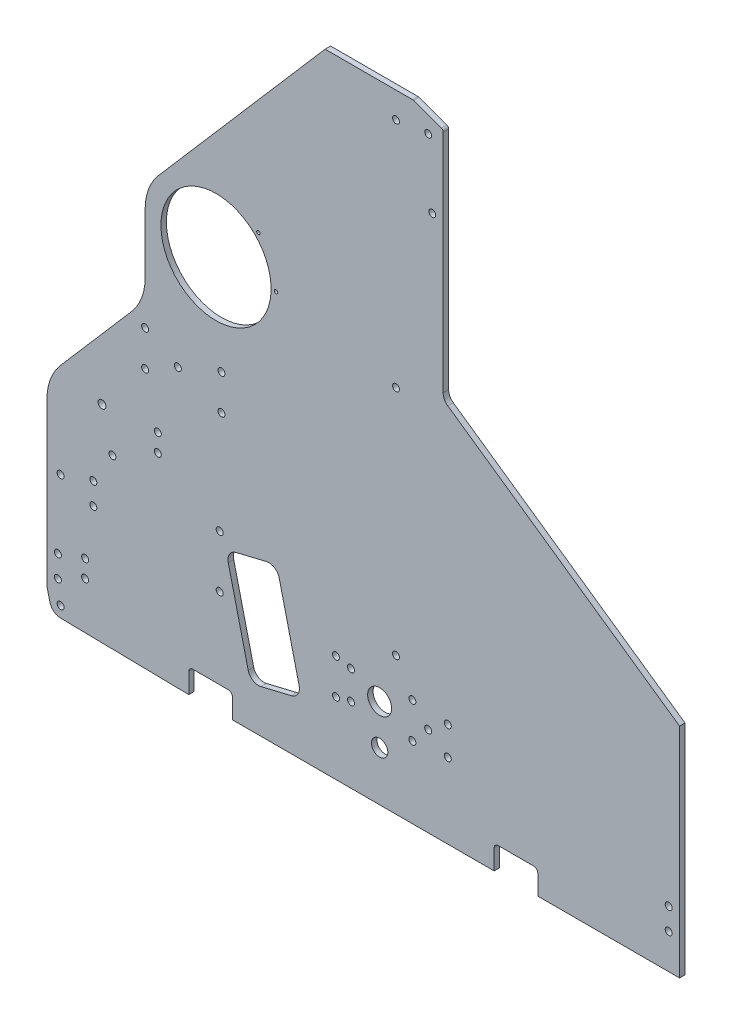
SolidWorks part; units mm, degrees
ref_plane "Front Plane" through (0, 0, 0) normal (0, 0, 1) x (1, 0, 0)
ref_plane "Top Plane" through (0, 0, 0) normal (0, 1, 0) x (1, 0, 0)
ref_plane "Right Plane" through (0, 0, 0) normal (1, 0, 0) x (0, 0, -1)
sketch "Sketch1" plane through (0, 0, 0) normal (0, 0, 1) x (1, 0, 0)
  line L0 (82.55, -20.32) -> (82.55, -6.35)
  line L2 (0, 0) -> (0, 157.48)
  line L4 (368.3, -20.32) -> (368.3, 106.68)
  line L5 (82.55, -6.35) -> (107.95, -6.35)
  line L6 (107.95, -6.35) -> (107.95, -20.32)
  line L7 (107.95, -20.32) -> (260.35, -20.32)
  line L8 (260.35, -20.32) -> (260.35, -6.35)
  line L9 (260.35, -6.35) -> (285.75, -6.35)
  line L10 (285.75, -6.35) -> (285.75, -20.32)
  line L11 (285.75, -20.32) -> (368.3, -20.32)
  line L12 (361.95, 12.7) -> (368.3, 12.7) construction
  line L13 (0, 0) -> (6.35, 0) construction
  line L14 (0.1896, -7.8901) -> (1.7771, -14.2401)
  line L15 (7.8295, -19.0491) -> (82.55, -20.32)
  line L16 (0, 0) -> (0, -6.35)
  line L17 (76.2, 141.605) -> (79.375, 141.605) construction
  line L18 (57.15, 131.2863) -> (101.6, 131.2862) construction
  line L19 (57.15, 131.2863) -> (57.15, 151.9238) construction
  line L20 (101.6, 131.2862) -> (101.6, 151.9237) construction
  line L21 (57.15, 151.9238) -> (101.6, 151.9237) construction
  line L22 (57.15, 131.2863) -> (101.6, 151.9237) construction
  line L23 (101.6, 131.2862) -> (57.15, 151.9238) construction
  line L25 (203.2, 59.805) -> (203.2, 194.805) construction
  line L26 (203.2, 194.805) -> (203.2, 329.805) construction
  line L27 (355.6, 332.105) -> (330.2, 332.105) construction
  line L28 (330.2, 332.105) -> (330.2, 217.805) construction
  line L29 (330.2, 217.805) -> (355.6, 217.805) construction
  line L30 (355.6, 217.805) -> (355.6, 332.105) construction
  line L31 (203.2, 344.805) -> (203.2, 194.805) construction
  line L32 (50.8, 332.105) -> (76.2, 332.105) construction
  line L33 (76.2, 332.105) -> (76.2, 217.805) construction
  line L34 (50.8, 217.805) -> (50.8, 332.105) construction
  line L35 (76.2, 217.805) -> (50.8, 217.805) construction
  line L36 (213.2, 344.805) -> (230.6638, 338.455)
  line L37 (203.2, 344.805) -> (161.925, 344.805)
  line L38 (203.2, 344.805) -> (213.2, 344.805)
  line L39 (348.5362, 344.805) -> (413.4623, 344.805)
  line L40 (348.5362, 344.805) -> (230.6638, 344.805) construction
  line L42 (161.925, 344.805) -> (0, 157.48)
  line L44 (230.6638, 338.455) -> (230.6638, 202.565)
  line L45 (230.6638, 202.565) -> (368.3, 106.68)
  line L46 (213.2, 344.805) -> (-141.0713, 344.805) construction
  circle A0 centre (6.35, 0) radius 2.032
  circle A1 centre (6.35, 12.7) radius 2.032
  circle A2 centre (361.95, 0) radius 2.032
  circle A3 centre (361.95, 12.7) radius 2.032
  arc A5 (1.7771, -14.2401) -> (7.8295, -19.0491) centre (7.9375, -12.7) ccw
  circle A6 centre (7.9375, -12.7) radius 2.032
  arc A7 (0, -6.35) -> (0.1896, -7.8901) centre (6.35, -6.35) ccw
  circle A8 centre (38.1, 78.105) radius 2.032
  circle A9 centre (76.2, 141.605) radius 2.032
  circle A10 centre (101.6, 131.2862) radius 2.032
  circle A11 centre (101.6, 151.9237) radius 2.032
  circle A12 centre (57.15, 151.9238) radius 2.032
  circle A13 centre (57.15, 131.2863) radius 2.032
  circle A15 centre (203.2, 59.805) radius 2
  circle A16 centre (203.2, 194.805) radius 2
  circle A17 centre (203.2, 329.805) radius 2
  circle A18 centre (63.5, 313.055) radius 2.032
  circle A20 centre (355.6, 332.105) radius 2.032
  circle A21 centre (330.2, 332.105) radius 2.032
  circle A22 centre (355.6, 217.805) radius 2.032
  circle A23 centre (330.2, 217.805) radius 2.032
  circle A24 centre (50.8, 332.105) radius 2.032
  circle A25 centre (76.2, 332.105) radius 2.032
  circle A26 centre (50.8, 217.805) radius 2.032
  circle A27 centre (76.2, 217.805) radius 2.032
  circle A28 centre (221.9319, 332.105) radius 2
  circle A29 centre (224.3138, 293.243) radius 2.032
  point P52 (0, 0)
  point P82 (203.2, 344.805)
  point P83 (221.9319, 341.63)
  dimension "D6" = 4.064
  dimension "D10" = 6.35
  dimension "D11" = 4.064
  dimension "D17" = 38.1
  dimension "D27" = 4
  dimension "D31" = 4.064
  dimension "D32" = 41.275
  dimension "D36" = 4.064
  dimension "D47" = 45.212
  dimension "D48" = 4.064
  dimension "D2" = 127
  dimension "D3" = 13.97
  dimension "D4" = 25.4
  dimension "D5" = 152.4
  dimension "D7" = 12.7
  dimension "D8" = 6.35
  dimension "D9" = 20.32
  dimension "D12" = 12.7
  dimension "D13" = 1.5875
  dimension "D14" = 82.55
  dimension "D15" = 368.3
  dimension "D16" = 6.35
  dimension "D18" = 98.425
  dimension "D19" = 38.1
  dimension "D20" = 63.5
  dimension "D21" = 3.175
  dimension "D22" = 270
  dimension "D23" = 20.6375
  dimension "D24" = 44.45
  dimension "D28" = 135
  dimension "D29" = 12.7
  dimension "D30" = 15
  dimension "D33" = 63.5
  dimension "D34" = 27.4638
  dimension "D37" = 114.3
  dimension "D38" = 25.4
  dimension "D39" = 12.7
  dimension "D40" = 157.48
  dimension "D41" = 142.24
  dimension "D42" = 365.125
  dimension "D43" = 10
  dimension "D44" = 6.35
  dimension "D45" = 31.75
  dimension "D46" = 6.35
  dimension "D49" = 6.35
  dimension "D50" = 203.2
extrude "Boss-Extrude1" add sketch "Sketch1" along normal blind 3.175 contours L16 A7 L14 A5 L15 L2 A0 A1 A6 region at (171.3968, 119.6345, 0)
fillet "Fillet1" radius 2.286 4 edges at (285.75, -6.35, 1.5875) (107.95, -6.35, 1.5875) (260.35, -6.35, 1.5875) (82.55, -6.35, 1.5875)
fillet "Fillet2" radius 6.35 1 edges at (230.6638, 202.565, 1.5875)
sketch "Sketch2" plane through (0, 0, 0) normal (0, 0, -1) x (-1, 0, 0)
  circle A0 centre (-100.5528, 71.086) radius 2.032 construction
  circle A1 centre (-100.5528, 40.606) radius 2.032 construction
  circle A2 centre (-22.225, 18.2025) radius 2.032 construction
  circle A3 centre (-22.225, 8.0425) radius 2.032 construction
  circle A4 centre (-100.5528, 71.086) radius 2.032
  circle A5 centre (-100.5528, 40.606) radius 2.032
  circle A6 centre (-22.225, 18.2025) radius 2.032
  circle A7 centre (-22.225, 8.0425) radius 2.032
extrude "Cut-Extrude1" cut sketch "Sketch2" against normal through all
fillet "Fillet3" radius 1.5875 2 edges at (230.6638, 338.455, 1.5875) (213.2, 344.805, 1.5875)
sketch "Sketch3" plane through (0, 0, 3.175) normal (0, 0, 1) x (1, 0, 0)
  line L0 (132.9524, 63.2646) -> (132.7215, 64.2281) construction
  line L1 (128.3814, 66.8897) -> (110.6828, 62.6472) construction
  line L2 (114.5132, 58.4237) -> (126.8822, 61.3887) construction
  line L3 (108.0212, 58.3071) -> (108.2522, 57.3436) construction
  line L4 (131.2006, 57.703) -> (140.0164, 20.9265) construction
  line L5 (144.0993, 16.7636) -> (132.9524, 63.2646) construction
  line L6 (108.2522, 57.3436) -> (119.3991, 10.8426) construction
  line L7 (121.1509, 16.4042) -> (112.3351, 53.1807) construction
  line L8 (119.3991, 10.8426) -> (119.6301, 9.8791) construction
  line L9 (144.3303, 15.8001) -> (144.0993, 16.7636) construction
  line L10 (137.8383, 15.6835) -> (125.4694, 12.7185) construction
  line L11 (123.9701, 7.2175) -> (141.6687, 11.4601) construction
  line L12 (132.9524, 63.2646) -> (132.7215, 64.2281)
  line L13 (128.3814, 66.8897) -> (110.6828, 62.6472)
  line L14 (114.5132, 58.4237) -> (126.8822, 61.3887)
  line L15 (108.0212, 58.3071) -> (108.2522, 57.3436)
  line L16 (131.2006, 57.703) -> (140.0164, 20.9265)
  line L17 (144.0993, 16.7636) -> (132.9524, 63.2646)
  line L18 (108.2522, 57.3436) -> (119.3991, 10.8426)
  line L19 (121.1509, 16.4042) -> (112.3351, 53.1807)
  line L20 (119.3991, 10.8426) -> (119.6301, 9.8791)
  line L21 (144.3303, 15.8001) -> (144.0993, 16.7636)
  line L22 (137.8383, 15.6835) -> (125.4694, 12.7185)
  line L23 (123.9701, 7.2175) -> (141.6687, 11.4601)
  line L24 (127.7894, 69.3598) -> (110.0908, 65.1172)
  line L25 (105.5512, 57.715) -> (105.7822, 56.7515)
  line L26 (105.7822, 56.7515) -> (116.9291, 10.2505)
  line L27 (116.9291, 10.2505) -> (117.16, 9.287)
  line L28 (124.5622, 4.7475) -> (142.2608, 8.99)
  line L29 (146.8003, 16.3922) -> (146.5694, 17.3557)
  line L30 (146.5694, 17.3557) -> (135.4225, 63.8567)
  line L31 (135.4225, 63.8567) -> (135.1915, 64.8202)
  line L32 (14.605, -0.1369) -> (103.7278, 32.3011) construction
  line L33 (14.605, -0.1369) -> (103.7278, 32.3011)
  line L35 (-39.6666, 74.7152) -> (103.7278, 126.9065) construction
  arc A0 (132.7215, 64.2281) -> (128.6308, 66.9403) centre (129.2206, 63.3889) ccw construction
  arc A1 (110.6828, 62.6472) -> (110.4377, 62.5791) centre (111.522, 59.1463) ccw construction
  arc A2 (128.6308, 66.9403) -> (128.3814, 66.8897) centre (129.2206, 63.3889) ccw construction
  arc A3 (110.4377, 62.5791) -> (108.0212, 58.3071) centre (111.522, 59.1463) ccw construction
  arc A4 (119.6301, 9.8791) -> (123.7207, 7.1669) centre (123.1309, 10.7183) ccw construction
  arc A5 (141.9139, 11.5281) -> (144.3303, 15.8001) centre (140.8295, 14.9609) ccw construction
  arc A6 (141.6687, 11.4601) -> (141.9139, 11.5281) centre (140.8295, 14.9609) ccw construction
  arc A7 (123.7207, 7.1669) -> (123.9701, 7.2175) centre (123.1309, 10.7183) ccw construction
  arc A8 (132.7215, 64.2281) -> (128.6308, 66.9403) centre (129.2206, 63.3889) ccw
  arc A9 (110.6828, 62.6472) -> (110.4377, 62.5791) centre (111.522, 59.1463) ccw
  arc A10 (128.6308, 66.9403) -> (128.3814, 66.8897) centre (129.2206, 63.3889) ccw
  arc A11 (110.4377, 62.5791) -> (108.0212, 58.3071) centre (111.522, 59.1463) ccw
  arc A12 (119.6301, 9.8791) -> (123.7207, 7.1669) centre (123.1309, 10.7183) ccw
  arc A13 (141.9139, 11.5281) -> (144.3303, 15.8001) centre (140.8295, 14.9609) ccw
  arc A14 (141.6687, 11.4601) -> (141.9139, 11.5281) centre (140.8295, 14.9609) ccw
  arc A15 (123.7207, 7.1669) -> (123.9701, 7.2175) centre (123.1309, 10.7183) ccw
  arc A16 (110.0908, 65.1172) -> (109.6726, 65.0012) centre (111.522, 59.1463) ccw
  arc A17 (109.6726, 65.0012) -> (105.5512, 57.715) centre (111.522, 59.1463) ccw
  arc A18 (117.16, 9.287) -> (124.1369, 4.6613) centre (123.1309, 10.7183) ccw
  arc A19 (124.1369, 4.6613) -> (124.5622, 4.7475) centre (123.1309, 10.7183) ccw
  arc A20 (142.2608, 8.99) -> (142.6789, 9.1061) centre (140.8295, 14.9609) ccw
  arc A21 (142.6789, 9.1061) -> (146.8003, 16.3922) centre (140.8295, 14.9609) ccw
  arc A22 (135.1915, 64.8202) -> (128.2147, 69.446) centre (129.2206, 63.3889) ccw
  arc A23 (128.2147, 69.446) -> (127.7894, 69.3598) centre (129.2206, 63.3889) ccw
  circle A24 centre (64.5259, 102.9405) radius 2.032 construction
  circle A25 centre (64.5259, 92.5258) radius 2.032 construction
  circle A26 centre (133.35, 208.2281) radius 1.016 construction
  circle A30 centre (26.9875, 46.9531) radius 2.032 construction
  circle A31 centre (26.9875, 59.6531) radius 2.032 construction
  circle A32 centre (7.9375, 53.3031) radius 2.032 construction
  circle A33 centre (26.9875, 46.9531) radius 2.032
  circle A34 centre (26.9875, 59.6531) radius 2.032
  circle A35 centre (7.9375, 53.3031) radius 2.032
  circle A37 centre (32.0306, 100.8109) radius 31.75 construction
  circle A38 centre (32.0306, 100.8109) radius 2.286
  circle A39 centre (123.1207, 232.9238) radius 1.016 construction
  circle A40 centre (64.5259, 102.9405) radius 2.032
  circle A41 centre (64.5259, 92.5258) radius 2.032
  circle A42 centre (133.35, 208.2281) radius 1.016
  circle A43 centre (123.1207, 232.9238) radius 1.016
  ellipse E0 centre (124.5974, 48.8487) end of major axis (128.5376, 61.3578) minor radius 6 (131.2006, 57.703) -> (126.8822, 61.3887) ccw construction
  ellipse E1 centre (122.2349, 48.2824) end of major axis (113.0518, 57.6456) minor radius 6 (114.5132, 58.4237) -> (112.3351, 53.1807) ccw construction
  ellipse E2 centre (127.7541, 25.2585) end of major axis (131.6942, 37.7675) minor radius 6 (121.1509, 16.4042) -> (125.4694, 12.7185) ccw construction
  ellipse E3 centre (130.1166, 25.8248) end of major axis (139.2998, 16.4616) minor radius 6 (137.8383, 15.6835) -> (140.0164, 20.9265) ccw construction
  ellipse E4 centre (124.5974, 48.8487) end of major axis (120.6573, 36.3397) minor radius 6 (131.2006, 57.703) -> (126.8822, 61.3887) ccw
  ellipse E5 centre (122.2349, 48.2824) end of major axis (131.4181, 38.9192) minor radius 6 (114.5132, 58.4237) -> (112.3351, 53.1807) ccw
  ellipse E6 centre (127.7541, 25.2585) end of major axis (131.6942, 37.7675) minor radius 6 (121.1509, 16.4042) -> (125.4694, 12.7185) ccw
  ellipse E7 centre (130.1166, 25.8248) end of major axis (139.2998, 16.4616) minor radius 6 (137.8383, 15.6835) -> (140.0164, 20.9265) ccw
  point P115 (32.0306, 100.8109)
  dimension "D3" = 63.5
  dimension "D4" = 4.572
  dimension "D2" = 88.9
  dimension "D1" = 2.54
extrude "Cut-Extrude2" cut sketch "Sketch3" against normal through all contours A22 A23 L24 A16 A17 L25 L26 L27 A18 A19 L28 A20 A21 L29 L30 L31 A15 A12 L20 L18 L15 A11 A9 L13 A10 A8 L12 L17 L21 A13 A14 L23 | A12 A15 L23 A14 A13 L21 L17 L12 A8 A10 L13 A9 A11 L15 L18 L20 E7 L22 E6 L19 E5 L14 E4 L16 | L22 E7 L16 E4 L14 E5 L19 E6 | A38 | A41 | A40 | A35 | A34 | A33 | A43 | A42 region at (137.844, 39.8506, 3.175) region at (126.1758, 37.0536, 3.175) region at (128.1544, 68.6507, 3.175) region at (32.0306, 100.8109, 3.175) region at (64.5259, 102.9405, 3.175) region at (64.5259, 92.5258, 3.175)
sketch "Sketch4" plane through (0, 0, 3.175) normal (0, 0, 1) x (1, 0, 0)
  line L0 (57.15, 151.9238) -> (101.6, 151.9237) construction
  line L1 (168.275, 21.4312) -> (212.725, 21.4312) construction
  line L2 (168.275, 21.4312) -> (168.275, 42.0687) construction
  line L3 (168.275, 42.0687) -> (212.725, 42.0687) construction
  line L4 (212.725, 21.4312) -> (212.725, 42.0687) construction
  line L5 (168.275, 21.4312) -> (212.725, 42.0687) construction
  line L6 (168.275, 42.0687) -> (212.725, 21.4312) construction
  line L7 (57.15, 131.2863) -> (57.15, 151.9238) construction
  line L8 (107.95, -20.32) -> (260.35, -20.32) construction
  line L9 (193.675, 31.75) -> (177.005, 31.75) construction
  line L10 (190.5, 31.75) -> (193.675, 31.75) construction
  line L11 (6.35, 12.7) -> (361.95, 12.7) construction
  line L12 (107.95, -6.35) -> (107.95, -20.32) construction
  line L13 (193.675, 31.75) -> (220.6625, 31.75) construction
  line L14 (177.005, 23.4569) -> (177.005, 40.0431) construction
  line L15 (213.2, 44.805) -> (193.2, 44.805) construction
  line L16 (213.2, 44.805) -> (213.2, 344.805) construction
  line L17 (213.2, 344.805) -> (193.2, 344.805) construction
  line L18 (193.2, 44.805) -> (193.2, 344.805) construction
  line L19 (213.2, 44.805) -> (193.2, 344.805) construction
  line L20 (213.2, 344.805) -> (193.2, 44.805) construction
  line L21 (226.9319, 332.105) -> (226.9319, 31.75) construction
  line L22 (237.33, 40.0431) -> (233.3612, 40.0431) construction
  line L23 (237.33, 23.4569) -> (233.3612, 23.4569) construction
  circle A0 centre (168.275, 42.0687) radius 2.032
  circle A1 centre (212.725, 42.0687) radius 2.032
  circle A2 centre (212.725, 21.4312) radius 2.032
  circle A3 centre (168.275, 21.4312) radius 2.032
  circle A4 centre (193.675, 31.75) radius 6.985
  circle A7 centre (220.6625, 31.75) radius 14.2875 construction
  circle A8 centre (193.675, 31.75) radius 12.7 construction
  circle A9 centre (177.005, 40.0431) radius 2.032
  circle A10 centre (177.005, 23.4569) radius 2.032
  circle A11 centre (237.33, 40.0431) radius 2.032 construction
  circle A12 centre (237.33, 23.4569) radius 2.032 construction
  circle A13 centre (193.675, 8.4667) radius 4.7625
  circle A14 centre (221.9319, 31.75) radius 2.032
  circle A15 centre (221.9319, 31.75) radius 5 construction
  circle A16 centre (221.9319, 332.105) radius 5 construction
  circle A17 centre (233.3612, 23.4569) radius 2.032
  circle A18 centre (233.3612, 40.0431) radius 2.032
  point P0 (190.5, 31.75)
  point P26 (203.2, 194.805)
  point P38 (177.005, 31.75)
  dimension "D1" = 4.064
  dimension "D4" = 13.97
  dimension "D7" = 9.525
  dimension "D10" = 25.4
  dimension "D11" = 28.575
  dimension "D16" = 10
  dimension "D17" = 4.064
  dimension "D18" = 10
  dimension "D2" = 52.07
  dimension "D3" = 3.175
  dimension "D5" = 82.55
  dimension "D6" = 26.9875
  dimension "D8" = 20
  dimension "D9" = 300
  dimension "D12" = 16.67
  dimension "D13" = 16.5862
  dimension "D14" = 60.325
  dimension "D15" = 23.2833
  dimension "D19" = 3.9688
extrude "Cut-Extrude3" cut sketch "Sketch4" against normal through all
sketch "Sketch5" plane through (0, 0, -187.325) normal (0, 0, -1) x (-1, 0, 0)
  line L0 (-57.15, 223.5947) -> (-57.15, 165.3337)
  line L1 (-161.925, 344.805) -> (-52.7201, 218.4699) construction
  line L2 (-57.15, 165.3337) -> (0, 99.219)
  line L3 (0, -6.35) -> (0, 157.48) construction
  line L4 (-50.4199, 215.8089) -> (0, 157.48) construction
  line L5 (-50.4199, 215.8089) -> (0, 157.48) construction
  line L6 (-57.15, 223.5947) -> (0, 157.48)
  line L7 (0, 157.48) -> (0, 99.219)
  circle A0 centre (-98.425, 208.2281) radius 32.0675
  dimension "D3" = 64.135
  dimension "D1" = 38.1
  dimension "D2" = 57.15
  dimension "D4" = 41.275
  dimension "D5" = 41.275
extrude "Cut-Extrude5" cut sketch "Sketch5" against normal through all contours A0 | L7 L6 L0 L2 region at (28.575, 161.4068, -187.325) region at (98.425, 208.2281, -187.325)
fillet "Fillet4" radius 31.75 3 edges at (0, 99.219, 1.5875) (57.15, 165.3337, 1.5875) (57.15, 223.5947, 1.5875)
